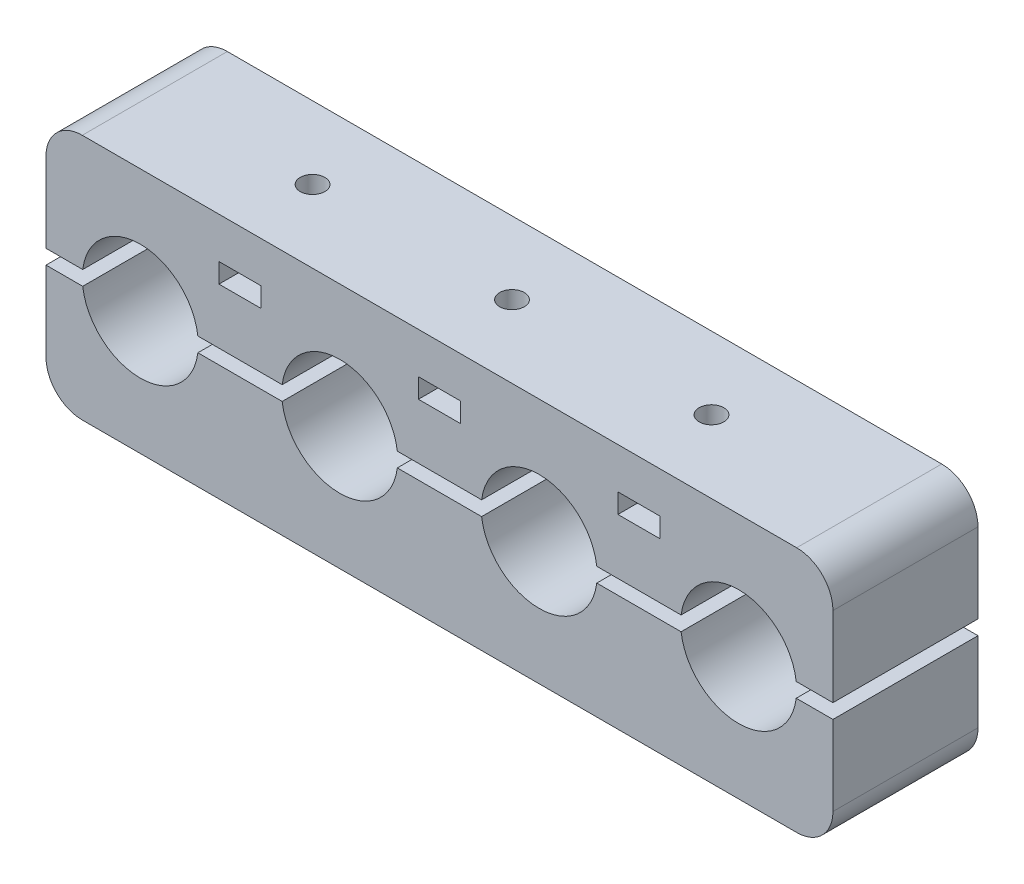
SolidWorks part; units mm, degrees
ref_plane "Piano frontale" through (0, 0, 0) normal (0, 0, 1) x (1, 0, 0)
ref_plane "Piano superiore" through (0, 0, 0) normal (0, 1, 0) x (1, 0, 0)
ref_plane "Piano destro" through (0, 0, 0) normal (1, 0, 0) x (0, 0, -1)
sketch "Schizzo1" plane through (0, 0, 0) normal (0, 0, 1) x (1, 0, 0)
  line L0 (0, 0) -> (-13, 0) construction
  line L1 (-13, 0) -> (-13, 17) construction
  line L2 (-13, 0) -> (-13, 1) construction
  line L3 (-8, 17) -> (90.5, 17)
  line L4 (-13, 12) -> (-13, -12)
  line L5 (-8, -17) -> (90.5, -17)
  line L6 (95.5, 12) -> (95.5, -12)
  line L8 (-13, 1) -> (95.5, 1)
  line L9 (-13, 1) -> (-13, -1)
  line L10 (-13, -1) -> (95.5, -1)
  line L11 (95.5, 1) -> (95.5, -1)
  circle A0 centre (0, 0) radius 8
  circle A1 centre (27.5, 0) radius 8
  circle A2 centre (55, 0) radius 8
  circle A3 centre (82.5, 0) radius 8
  circle A6 centre (0, 0) radius 11.5 construction
  arc A7 (90.5, 17) -> (95.5, 12) centre (90.5, 12) cw
  arc A8 (90.5, -17) -> (95.5, -12) centre (90.5, -12) ccw
  arc A9 (-13, -12) -> (-8, -17) centre (-8, -12) ccw
  arc A10 (-13, 12) -> (-8, 17) centre (-8, 12) cw
  point P28 (0, 0)
  point P29 (0, 0)
  dimension "D1" = 4
  dimension "D2" = 5
extrude "Estrusione-Estrusione1" add sketch "Schizzo1" along normal blind 20 contours A10 L4 L8 A0 A1 A2 A3 L6 A7 L3 | L4 A9 L5 A8 L6 L10 A3 A2 A1 A0 region at (41.25, 10.1805, 0) region at (41.25, -10.1805, 0)
sketch "Schizzo2" plane through (0, 0, 20) normal (0, 0, 1) x (1, 0, 0)
  line L0 (13.75, 1) -> (13.75, 17) construction
  line L1 (7.9373, 1) -> (19.5627, 1) construction
  line L2 (-8, 17) -> (90.5, 17) construction
  line L3 (41.25, 1) -> (41.25, 17) construction
  line L5 (35.4373, 1) -> (47.0627, 1) construction
  line L6 (68.75, 1) -> (68.75, 17) construction
  line L7 (62.9373, 1) -> (74.5627, 1) construction
  line L8 (13.75, 17) -> (13.75, 10) construction
  line L9 (10.85, 8.65) -> (16.65, 8.65)
  line L10 (10.85, 8.65) -> (10.85, 11.35)
  line L11 (16.65, 8.65) -> (16.65, 11.35)
  line L12 (10.85, 11.35) -> (16.65, 11.35)
  line L13 (10.85, 8.65) -> (16.65, 11.35) construction
  line L14 (16.65, 8.65) -> (10.85, 11.35) construction
  line L15 (38.35, 11.35) -> (44.15, 11.35)
  line L16 (38.35, 8.65) -> (44.15, 8.65)
  line L17 (38.35, 8.65) -> (38.35, 11.35)
  line L18 (44.15, 8.65) -> (44.15, 11.35)
  line L19 (65.85, 11.35) -> (71.65, 11.35)
  line L20 (65.85, 8.65) -> (71.65, 8.65)
  line L21 (65.85, 8.65) -> (65.85, 11.35)
  line L22 (71.65, 8.65) -> (71.65, 11.35)
  dimension "D1" = 3
extrude "Taglio-Estrusione1" cut sketch "Schizzo2" against normal blind 20
sketch "Schizzo3" plane through (0, -17, 0) normal (0, -1, 0) x (1, 0, 0)
  line L0 (41.25, 20) -> (41.25, 0) construction
  line L1 (-8, 20) -> (90.5, 20) construction
  line L2 (-8, 0) -> (90.5, 0) construction
  line L3 (41.25, 10) -> (68.75, 10) construction
  line L4 (41.25, 10) -> (13.75, 10) construction
hole_wizard "Foro per Vite M3-1" positions "Schizzo4" profile "Schizzo5" hole size "M3" standard "Ansi Metric"
sketch "Schizzo4" plane through (0, -17, 0) normal (0, -1, 0) x (-1, 0, 0)
  point P0 (-68.75, -10)
  point P3 (-41.25, -10)
  point P6 (-13.75, -10)
sketch "Schizzo5" plane through (68.75, -17, 10) normal (1, 0, 0) x (0, 0, -1)
  line L0 (0, 0) -> (0, 40)
  line L1 (0, 40) -> (1.7, 38.9785)
  line L2 (1.7, 38.9785) -> (1.7, 0)
  line L5 (1.7, 0) -> (0, 0)
  line L10 (0, 40) -> (-1.7, 38.9785) construction
  line L11 (0, -6.35) -> (0, 107.95) construction
  dimension "Hole Dia." = 3.4
  dimension "Hole Depth" = 40
  dimension "Drill Angle" = 118
